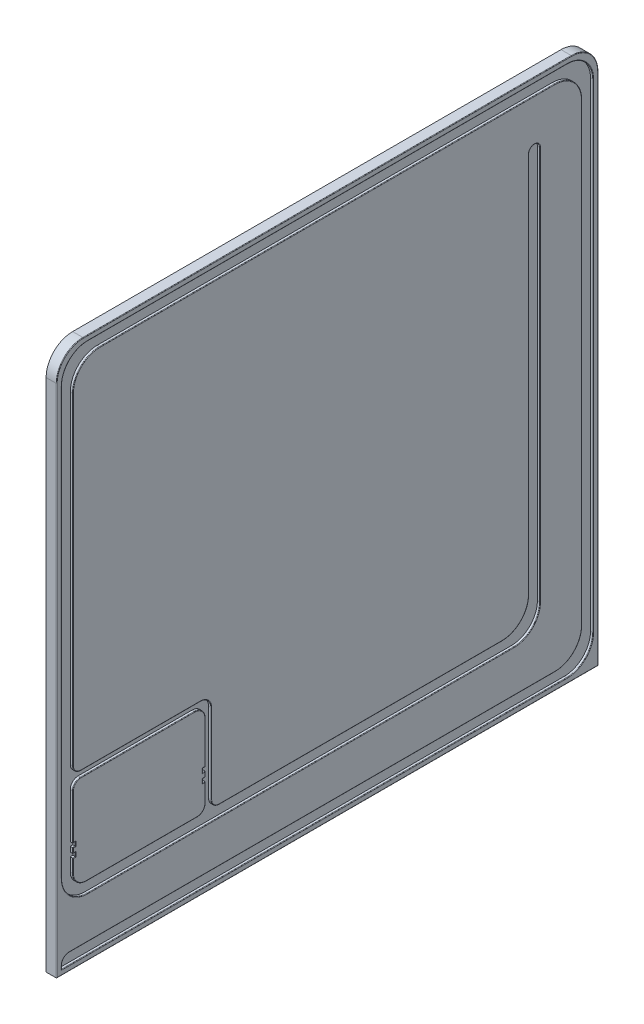
SolidWorks part; units mm, degrees
ref_plane "Front Plane" through (0, 0, 0) normal (0, 0, 1) x (1, 0, 0)
ref_plane "Top Plane" through (0, 0, 0) normal (0, 1, 0) x (1, 0, 0)
ref_plane "Right Plane" through (0, 0, 0) normal (1, 0, 0) x (0, 0, -1)
sketch "Sketch1" plane through (0, 0, 0) normal (1, 0, 0) x (0, 0, -1)
  line L1 (-102, -102) -> (102, -102)
  line L2 (-102, -102) -> (-102, 92)
  line L3 (-92, 102) -> (92, 102)
  line L4 (102, -102) -> (102, 92)
  line L5 (-102, -102) -> (102, 102) construction
  line L6 (-102, 102) -> (102, -102) construction
  arc A2 (-102, 92) -> (-92, 102) centre (-92, 92) cw
  arc A3 (92, 102) -> (102, 92) centre (92, 92) cw
  point P0 (0, 0)
  dimension "D1" = 204
  dimension "D2" = 204
extrude "Boss-Extrude1" add sketch "Sketch1" along normal blind 4
sketch "Sketch2" plane through (4, 0, 0) normal (1, 0, 0) x (0, 0, -1)
  line L40 (-100.1, 90.3) -> (-100.1, -70.3)
  line L41 (-90.3, 100.1) -> (90.3, 100.1)
  line L42 (100.1, 90.3) -> (100.1, -90.3)
  line L43 (90.3, -100.1) -> (-100.1, -100.1)
  line L44 (-100.1, -100.1) -> (-100.1, -98.7)
  line L45 (-97.3, -95.9) -> (85.7, -95.9)
  line L46 (85.7, 95.9) -> (-85.7, 95.9)
  line L47 (-95.9, 85.7) -> (-95.9, -35.8)
  line L48 (-90.9, -75.9) -> (-49, -75.9)
  line L49 (75.9, -65.7) -> (75.9, 78)
  line L50 (-90.3, -80.1) -> (70.3, -80.1)
  line L51 (95.9, -85.7) -> (95.9, 85.7)
  line L52 (80.1, 78) -> (80.1, -70.3)
  line L55 (-92.9, -41) -> (-50, -41)
  line L56 (-46, -45) -> (-46, -61)
  line L57 (-43.8, -72.9) -> (-43.8, -42.8)
  line L58 (-47.8, -38.8) -> (-92.9, -38.8)
  line L59 (-95.9, -44) -> (-95.9, -61)
  line L60 (-40.8, -75.9) -> (65.7, -75.9)
  line L61 (-95.9, -61) -> (-94.9, -61)
  line L62 (-94.9, -61) -> (-94.9, -62.5)
  line L63 (-94.9, -62.5) -> (-95.9, -62.5)
  line L64 (-95.9, -64.4) -> (-94.9, -64.4)
  line L65 (-94.9, -64.4) -> (-94.9, -65.9)
  line L66 (-94.9, -65.9) -> (-95.9, -65.9)
  line L67 (-95.9, -62.5) -> (-95.9, -64.4)
  line L68 (-95.9, -65.9) -> (-95.9, -70.9)
  line L69 (-46, -61) -> (-47, -61)
  line L70 (-47, -61) -> (-47, -62.5)
  line L71 (-47, -62.5) -> (-46, -62.5)
  line L72 (-46, -65.9) -> (-47, -65.9)
  line L73 (-47, -65.9) -> (-47, -64.4)
  line L74 (-47, -64.4) -> (-46, -64.4)
  line L75 (-46, -62.5) -> (-46, -64.4)
  line L76 (-46, -65.9) -> (-46, -72.9)
  line L77 (92, 102) -> (-92, 102) construction
  line L78 (-102, 92) -> (-102, -102) construction
  arc A32 (-95.9, -70.9) -> (-90.9, -75.9) centre (-90.9, -70.9) ccw
  arc A33 (65.7, -75.9) -> (75.9, -65.7) centre (65.7, -65.7) ccw
  arc A34 (-85.7, 95.9) -> (-95.9, 85.7) centre (-85.7, 85.7) ccw
  arc A35 (-100.1, 90.3) -> (-90.3, 100.1) centre (-90.3, 90.3) cw
  arc A36 (100.1, -90.3) -> (90.3, -100.1) centre (90.3, -90.3) cw
  arc A37 (85.7, -95.9) -> (95.9, -85.7) centre (85.7, -85.7) ccw
  arc A38 (80.1, -70.3) -> (70.3, -80.1) centre (70.3, -70.3) cw
  arc A39 (85.7, 95.9) -> (95.9, 85.7) centre (85.7, 85.7) cw
  arc A40 (90.3, 100.1) -> (100.1, 90.3) centre (90.3, 90.3) cw
  arc A41 (75.9, 78) -> (80.1, 78) centre (78, 78) cw
  arc A42 (-100.1, -98.7) -> (-97.3, -95.9) centre (-97.3, -98.7) cw
  arc A43 (-100.1, -70.3) -> (-90.3, -80.1) centre (-90.3, -70.3) ccw
  arc A44 (-43.8, -42.8) -> (-47.8, -38.8) centre (-47.8, -42.8) ccw
  arc A45 (-50, -41) -> (-46, -45) centre (-50, -45) cw
  arc A46 (-40.8, -75.9) -> (-43.8, -72.9) centre (-40.8, -72.9) cw
  arc A47 (-92.9, -38.8) -> (-95.9, -35.8) centre (-92.9, -35.8) cw
  arc A48 (-46, -72.9) -> (-49, -75.9) centre (-49, -72.9) cw
  arc A49 (-92.9, -41) -> (-95.9, -44) centre (-92.9, -44) ccw
  point P107 (-95.4, -64.4)
  dimension "D26" = 4.2
  dimension "D27" = 10.2
  dimension "D9" = 34.9
  dimension "D35" = 9.8
  dimension "D30" = 10.2
  dimension "D31" = 9.8
  dimension "D41" = 10.2
  dimension "D42" = 9.8
  dimension "D43" = 10.2
  dimension "D44" = 9.8
  dimension "D47" = 2.8
  dimension "D48" = 9.8
  dimension "D49" = 5
  dimension "D52" = 4
  dimension "D53" = 3
  dimension "D54" = 3
  dimension "D1" = 1.9
  dimension "D7" = 1.9
  dimension "D8" = 49.9
  dimension "D21" = 4.2
  dimension "D22" = 4.2
  dimension "D23" = 4.2
  dimension "D25" = 15.8
  dimension "D36" = 200.2
  dimension "D37" = 200.2
  dimension "D38" = 4.2
  dimension "D39" = 15.8
  dimension "D40" = 4.2
  dimension "D45" = 2.1
  dimension "D46" = 15.8
  dimension "D50" = 2.2
  dimension "D51" = 2.2
  dimension "D55" = 1.5
  dimension "D56" = 1.9
  dimension "D57" = 1
  dimension "D58" = 20
  dimension "D59" = 1.9
  dimension "D60" = 1
extrude "Cut-Extrude3" cut sketch "Sketch2" against normal blind 1
fillet "Fillet1" radius 0.2 59 edges at (4, -102, 0) (4, -5, 102) (4, 99.0711, 99.0711) (4, 102, 0) (4, 99.0711, -99.0711) (4, -5, -102) (4, -72.9125, -72.9125) (4, -75.9, -12.45) (4, -75.0213, 42.9213) (4, -57.85, 43.8) (4, -39.9716, 44.9716) (4, -38.8, 70.35) (4, -37.9213, 95.0213) (4, 24.95, 95.9) (4, 92.9125, 92.9125) (4, 95.9, 0) (4, 92.9125, -92.9125) (4, 0, -95.9) (4, -92.9125, -92.9125) (4, -95.9, 5.8) (4, -96.7201, 99.2799) (4, -99.4, 100.1) (4, -100.1, 4.9) (4, -97.2296, -97.2296) (4, 0, -100.1) (4, 97.2296, -97.2296) (4, 100.1, 0) (4, 97.2296, 97.2296) (4, 10, 100.1) (4, -77.2296, 97.2296) (4, -80.1, 10) (4, -77.2296, -77.2296) (4, 3.85, -80.1) (4, 80.1, -78) (4, 6.15, -75.9) (4, -68.4, 95.9) (4, -65.9, 95.4) (4, -65.15, 94.9) (4, -64.4, 95.4) (4, -63.45, 95.9) (4, -62.5, 95.4) (4, -61.75, 94.9) (4, -61, 95.4) (4, -52.5, 95.9) (4, -41.8787, 95.0213) (4, -41, 71.45) (4, -42.1716, 47.1716) (4, -53, 46) (4, -61, 46.5) (4, -61.75, 47) (4, -62.5, 46.5) (4, -63.45, 46) (4, -64.4, 46.5) (4, -65.15, 47) (4, -65.9, 46.5) (4, -69.4, 46) (4, -75.0213, 46.8787) (4, -75.9, 69.95) (4, -74.4355, 94.4355)
